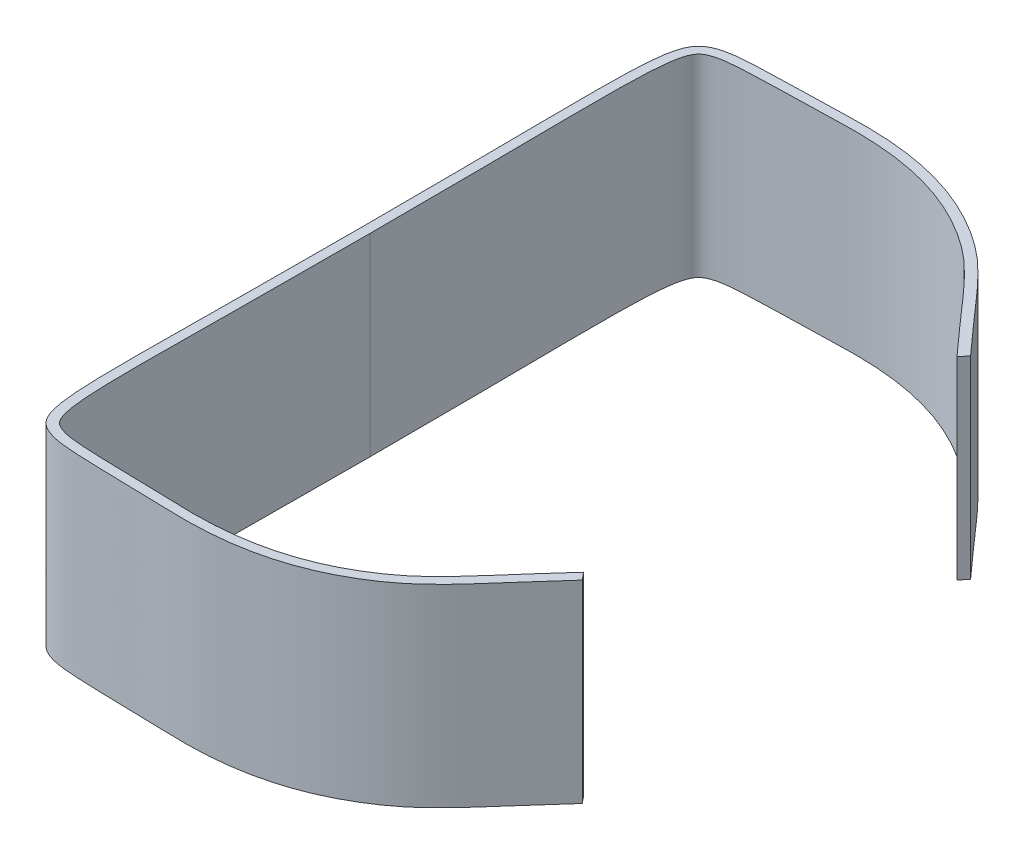
SolidWorks part; units mm, degrees
material "PLA"
ref_plane "Front Plane" through (0, 0, 0) normal (0, 0, 1) x (1, 0, 0)
ref_plane "Top Plane" through (0, 0, 0) normal (0, 1, 0) x (1, 0, 0)
ref_plane "Right Plane" through (0, 0, 0) normal (1, 0, 0) x (0, 0, -1)
sketch "Sketch1" plane through (0, 0, 0) normal (0, 1, 0) x (1, 0, 0)
  arc A0 (31.3497, -38.0693) -> (31.3497, -12.0693) centre (31.3497, -25.0693) ccw
  arc A1 (31.3497, -40.0693) -> (31.3497, -10.0693) centre (31.3497, -25.0693) ccw
  arc A2 (31.3497, -40.0693) -> (31.3497, -10.0693) centre (31.3497, -25.0693) ccw
  spline S0 degree 1 poles (31.3497, -12.0693) (-102.5003, -25.0693) knots 0 0 1 1 construction
  spline S1 degree 1 poles (-102.5003, -25.0693) (31.3497, -38.0693) knots 0 0 1 1 construction
  spline S2 degree 3 poles (-400.1867, 2959.4431) (-21.4012, -21.4544) (-130.2028, -87.9365) (-95.1723, -95.9434) (-79.4693, -96.0745) (-63.666, -96.7855) (-48.6034, -94.7613) (-29.9398, -81.014) (-19.6588, -67.0508) (54.3895, 2.5485) (-156.7681, -142.3186) (3017.9127, 231.9123) knots -0.897514 -0.897514 -0.897514 -0.897514 0.317928 0.363507 0.445537 0.481033 0.682965 0.721704 0.829683 0.858862 1.493222 1.493222 1.493222 1.493222 only from (-104.5003, -25.0693) to (31.3497, -40.0693)
  spline S3 degree 3 poles (3018.125, -282.0759) (-156.7771, 92.1863) (54.3908, -52.6883) (-19.6588, 16.9123) (-29.9398, 30.8755) (-48.6034, 44.6228) (-63.666, 46.647) (-79.4693, 45.936) (-95.1723, 45.8048) (-130.2026, 37.798) (-21.4021, -28.6836) (-400.1816, -3009.5417) knots -0.493237 -0.493237 -0.493237 -0.493237 0.141138 0.170317 0.278296 0.317035 0.518967 0.554463 0.636493 0.682072 1.897508 1.897508 1.897508 1.897508 only from (31.3497, -10.0693) to (-104.5003, -25.0693)
  spline S4 degree 3 poles (-104.5003, -25.0693) (-104.5003, -86.2204) (-106.7931, -93.2872) (-95.1723, -95.9434) (-79.4693, -96.0745) (-63.666, -96.7855) (-48.6034, -94.7613) (-29.9398, -81.014) (-19.6588, -67.0508) (7.0513, -41.9455) (5.2901, -40.0693) (31.3497, -40.0693) knots 0 0 0 0 0.317928 0.363507 0.445537 0.481033 0.682965 0.721704 0.829683 0.858862 1 1 1 1
  spline S5 degree 3 poles (31.3497, -10.0693) (5.2901, -10.0693) (7.0513, -8.1931) (-19.6588, 16.9123) (-29.9398, 30.8755) (-48.6034, 44.6228) (-63.666, 46.647) (-79.4693, 45.936) (-95.1723, 45.8048) (-106.7931, 43.1487) (-104.5003, 36.0818) (-104.5003, -25.0693) knots 0 0 0 0 0.141138 0.170317 0.278296 0.317035 0.518967 0.554463 0.636493 0.682072 1 1 1 1
  spline S6 degree 3 poles (31.3497, -12.0693) (30.6468, -12.0693) (29.2115, -12.0669) (27.235, -12.0551) (25.3574, -12.0342) (23.0041, -11.9927) (20.3185, -11.9127) (17.4651, -11.7629) (14.9349, -11.5501) (11.9328, -11.1676) (8.7634, -10.4751) (5.5939, -9.1883) (2.8815, -7.4107) (0.3957, -5.2059) (-2.2321, -2.5476) (-5.3567, 0.6457) (-9.4125, 4.5375) (-13.7609, 8.7579) (-17.6868, 12.8509) (-21.2594, 16.7718) (-25.6093, 21.7088) (-30.4043, 27.2348) (-35.451, 32.4023) (-40.235, 35.9702) (-45.0957, 38.7908) (-49.9382, 40.9204) (-54.7711, 42.4536) (-59.5761, 43.47) (-63.5451, 43.9533) (-66.6901, 44.1607) (-69.0303, 44.2365) (-71.3534, 44.2428) (-73.6409, 44.1878) (-76.1322, 44.0974) (-79.1488, 44.0116) (-82.6311, 43.9404) (-86.2768, 43.8639) (-89.829, 43.7689) (-93.0248, 43.6408) (-95.5383, 43.4676) (-97.2067, 43.2452) (-98.295, 42.998) (-99.1661, 42.7038) (-99.8642, 42.3895) (-100.3677, 42.0598) (-100.7648, 41.6822) (-101.2544, 40.9991) (-101.8532, 39.5166) (-102.3837, 36.3278) (-102.6794, 31.5686) (-102.7834, 25.0125) (-102.7581, 17.8377) (-102.7019, 10.9332) (-102.6496, 5.1373) (-102.5949, -1.3117) (-102.5539, -7.2599) (-102.5279, -12.3813) (-102.5126, -16.4069) (-102.5044, -19.9238) (-102.5009, -22.8265) (-102.5003, -24.3257) (-102.5003, -25.0693) knots 0 0 0 0 0.003906 0.007812 0.011719 0.015625 0.023438 0.03125 0.039062 0.046875 0.0625 0.078125 0.09375 0.109375 0.125 0.140625 0.15625 0.171875 0.1875 0.203125 0.21875 0.25 0.28125 0.3125 0.34375 0.375 0.40625 0.4375 0.46875 0.484375 0.5 0.515625 0.53125 0.546875 0.5625 0.578125 0.59375 0.609375 0.625 0.640625 0.65625 0.671875 0.6875 0.703125 0.71875 0.734375 0.75 0.78125 0.8125 0.84375 0.875 0.90625 0.921875 0.9375 0.953125 0.96875 0.976562 0.984375 0.992188 0.996094 1 1 1 1
  spline S7 degree 3 poles (-102.5003, -25.0693) (-102.5003, -25.8129) (-102.5009, -27.312) (-102.5044, -30.2147) (-102.5126, -33.7316) (-102.5279, -37.7573) (-102.5539, -42.8787) (-102.5949, -48.8268) (-102.6496, -55.2759) (-102.7019, -61.0718) (-102.7581, -67.9762) (-102.7834, -75.151) (-102.6794, -81.7071) (-102.3837, -86.4663) (-101.8532, -89.6552) (-101.2544, -91.1377) (-100.7648, -91.8208) (-100.3677, -92.1983) (-99.8642, -92.528) (-99.1661, -92.8424) (-98.295, -93.1366) (-97.2067, -93.3837) (-95.5383, -93.6062) (-93.0248, -93.7794) (-89.829, -93.9074) (-86.2768, -94.0024) (-82.6311, -94.079) (-79.1488, -94.1501) (-76.1322, -94.2359) (-73.6409, -94.3263) (-71.3534, -94.3813) (-69.0303, -94.375) (-66.6901, -94.2993) (-63.5451, -94.0918) (-59.5761, -93.6086) (-54.7711, -92.5921) (-49.9382, -91.059) (-45.0957, -88.9293) (-40.235, -86.1088) (-35.451, -82.5409) (-30.4043, -77.3733) (-25.6093, -71.8473) (-21.2594, -66.9103) (-17.6868, -62.9895) (-13.7609, -58.8964) (-9.4125, -54.6761) (-5.3567, -50.7842) (-2.2321, -47.591) (0.3957, -44.9326) (2.8815, -42.7279) (5.5939, -40.9502) (8.7634, -39.6634) (11.9328, -38.9709) (14.9349, -38.5885) (17.4651, -38.3756) (20.3185, -38.2259) (23.0041, -38.1459) (25.3574, -38.1043) (27.235, -38.0834) (29.2115, -38.0717) (30.6468, -38.0693) (31.3497, -38.0693) knots 0 0 0 0 0.003906 0.007812 0.015625 0.023438 0.03125 0.046875 0.0625 0.078125 0.09375 0.125 0.15625 0.1875 0.21875 0.25 0.265625 0.28125 0.296875 0.3125 0.328125 0.34375 0.359375 0.375 0.390625 0.40625 0.421875 0.4375 0.453125 0.46875 0.484375 0.5 0.515625 0.53125 0.5625 0.59375 0.625 0.65625 0.6875 0.71875 0.75 0.78125 0.796875 0.8125 0.828125 0.84375 0.859375 0.875 0.890625 0.90625 0.921875 0.9375 0.953125 0.960938 0.96875 0.976562 0.984375 0.988281 0.992188 0.996094 1 1 1 1
  dimension "D1" = 0
  dimension "D2" = 2
extrude "Boss-Extrude1" add sketch "Sketch1" along normal up to surface (40.5 mm away)
sketch "Sketch2" plane through (0, 40.5, 0) normal (0, 1, 0) x (1, 0, 0)
  circle A0 centre (31.3497, -25.0693) radius 63.5 construction
  circle A1 centre (31.3497, -25.0693) radius 63.5
extrude "Cut-Extrude1" cut sketch "Sketch2" against normal through all
